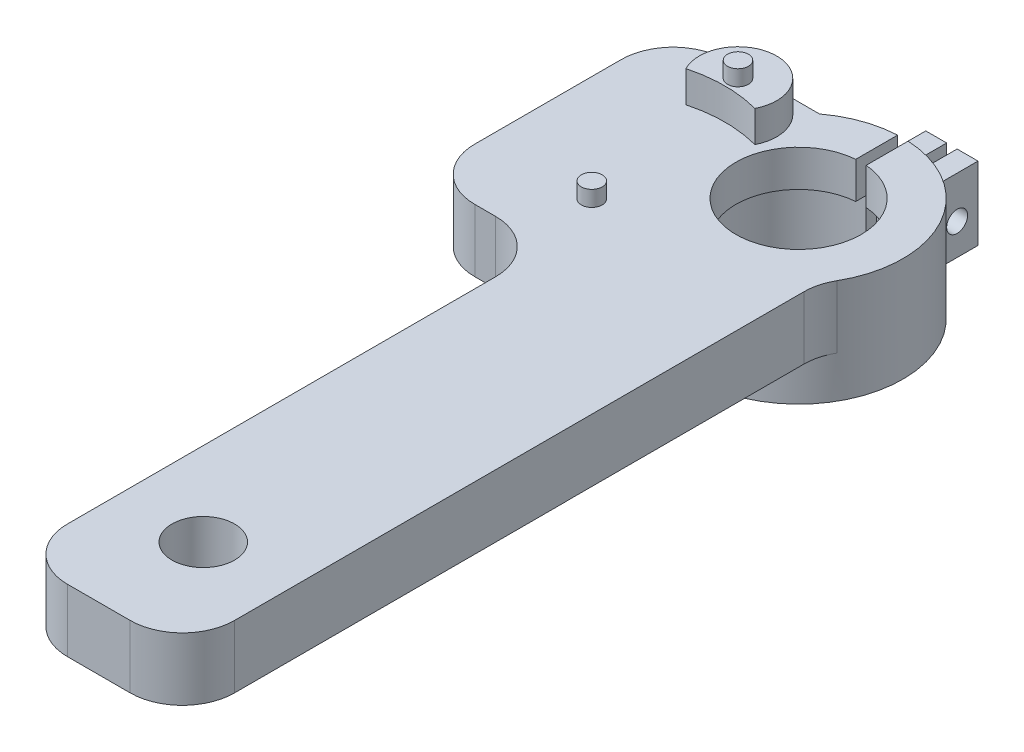
SolidWorks part; units mm, degrees
material "ABS"
ref_plane "Front Plane" through (0, 0, 0) normal (0, 0, 1) x (1, 0, 0)
ref_plane "Top Plane" through (0, 0, 0) normal (0, 1, 0) x (1, 0, 0)
ref_plane "Right Plane" through (0, 0, 0) normal (1, 0, 0) x (0, 0, -1)
sketch "BaseArm" plane through (0, 0, 0) normal (0, 1, 0) x (1, 0, 0)
  line L1 (-8, 0) -> (8, 0)
  line L2 (-8, 0) -> (-8, 62)
  line L3 (-8, 62) -> (8, 62) construction
  line L4 (8, 0) -> (8, 62)
  arc A0 (-8, 62) -> (8, 62) centre (0, 69.6738) ccw
  dimension "D1" = 8
  dimension "D2" = 8
  dimension "D3" = 62
extrude "Boss-Extrude1" add sketch "BaseArm" along normal blind 6
sketch "Sketch2" plane through (0, 0, 0) normal (0, 1, 0) x (1, 0, 0)
  circle A2 centre (0, 67) radius 10
  circle A3 centre (0, 67) radius 7
  dimension "D1" = 14
  dimension "D2" = 20
  dimension "D3" = 67
extrude "Boss-Extrude2" add sketch "Sketch2" along normal blind 6
ref_axis "Axis1" through (0, 7.6937, -67) along (0, -1, 0)
ref_plane "Plane1" through (0, 0, -67) normal (0, 0, 1) x (0, -1, 0)
ref_plane "Plane2" through (0, 0, -77) normal (0, 0, -1) x (-1, 0, 0)
sketch "Sketch14" plane through (0, 0, -77) normal (0, 0, -1) x (-1, 0, 0)
  line L1 (-3, 0) -> (3, 0)
  line L2 (-3, 0) -> (-3, 10)
  line L3 (-3, 10) -> (3, 10)
  line L4 (3, 0) -> (3, 10)
  line L5 (-10, 0) -> (10, 0) construction
  line L6 (0, 7.6937) -> (0, 2.7565) construction
  dimension "D1" = 10
  dimension "D2" = 0
  dimension "D3" = 3
  dimension "D4" = 3
sketch "Sketch24" plane through (0, 0, 0) normal (0, -1, 0) x (1, 0, 0)
  circle A0 centre (0, -67) radius 7
  circle A1 centre (0, -67) radius 10
  arc A2 (-8, -61) -> (8, -61) centre (0, -67) ccw construction
  circle A3 centre (0, -67) radius 7 construction
extrude "Boss-Extrude8" add sketch "Sketch24" along normal blind 4
sketch "Sketch26" plane through (0, 6, 0) normal (0, 1, 0) x (1, 0, 0)
  circle A0 centre (0, 67) radius 7
  circle A1 centre (0, 67) radius 7 construction
  circle A2 centre (0, 67) radius 6
  dimension "D1" = 1
extrude "Boss-Extrude9" add sketch "Sketch26" against normal blind 3.5
sketch "Sketch6" plane through (0, 0, 0) normal (0, 1, 0) x (1, 0, 0)
  line L6 (0, -7.975) -> (0, 7.975) construction
  line L11 (0.5, 83.4083) -> (-0.5, 83.4083)
  line L13 (0.5, 72.3952) -> (-0.5, 72.3952)
  line L14 (-0.5, 83.4083) -> (-0.5, 72.3952)
  line L15 (0.5, 83.4083) -> (0.5, 72.3952)
  dimension "D1" = 1
extrude "Cut-Extrude2" cut sketch "Sketch6" along normal through all and the other way through all
hole_wizard "Ø6.0mm Dowel Hole1" positions "3DSketch3" profile "Sketch9" hole size "Ø6.0" standard "ISO" end condition through all
sketch3d "3DSketch3"
  line L2 (-8, 6, 0) -> (8, 6, 0) construction
  line L3 (0, 6, 0) -> (0, 6, -10) construction
  point P0 (0, 6, -10)
  dimension "D2" = 10
sketch "Sketch9" plane through (0, 6, -10) normal (1, 0, 0) x (0, 0, 1)
  line L0 (0, 0) -> (0, 10)
  line L1 (0, 10) -> (3, 10)
  line L2 (3, 10) -> (3, 0)
  line L5 (3, 0) -> (0, 0)
  line L11 (0, -6.35) -> (0, 107.95) construction
  dimension "Thru Hole Dia." = 6
  dimension "Thru Hole Depth" = 10
sketch "Sketch10" plane through (0, 0, 0) normal (0, 1, 0) x (1, 0, 0)
  line L0 (0, -7.975) -> (0, 7.975) construction
  line L1 (0.5, 0) -> (-0.5, 0)
  line L3 (0.5, 8.5942) -> (-0.5, 8.5942)
  line L4 (-0.5, 0) -> (-0.5, 8.5942)
  line L5 (0.5, 0) -> (0.5, 8.5942)
sketch "Sketch11" plane through (0, 0, 0) normal (0, 1, 0) x (1, 0, 0)
  line L0 (-8, 61) -> (-8, 0) construction
  line L1 (-8, 15.2461) -> (-6, 15.2461)
  line L2 (-8, 15.2461) -> (-8, 57.0454)
  line L3 (-8, 57.0454) -> (-6, 57.0454)
  line L4 (-6, 15.2461) -> (-6, 57.0454)
  line L5 (0, -55) -> (0, 55) construction
  line L6 (8, 57.0454) -> (6, 57.0454)
  line L7 (6, 15.2461) -> (6, 57.0454)
  line L8 (8, 15.2461) -> (6, 15.2461)
  line L9 (8, 15.2461) -> (8, 57.0454)
  dimension "D1" = 2
extrude "Cut-Extrude4" [suppressed] cut sketch "Sketch11" along normal blind 8
ref_point "Point1"
sketch "Sketch27" plane through (0, 6, 0) normal (0, 1, 0) x (1, 0, 0)
  line L0 (-4, 54.5362) -> (-4, 59.5362)
  line L2 (-4, 54.5362) -> (-14, 54.5362)
  line L3 (-14, 54.5362) -> (-14, 75.5362)
  line L4 (-14, 75.5362) -> (-4, 75.5362)
  line L5 (-4, 75.5362) -> (-4, 74.4638)
  arc A0 (-4, 74.4638) -> (-4, 59.5362) centre (0, 67) ccw
  point P1 (-4, 54.5362)
  point P5 (0, 0)
  point P6 (0, 0)
  point P7 (0, 0)
  dimension "D5" = 8.4681
  dimension "D1" = 5
  dimension "D2" = 10
  dimension "D3" = 21
  dimension "D4" = 4
extrude "Boss-Extrude12" [suppressed] add sketch "Sketch27" against normal up to vertex
sketch "Sketch17" plane through (0, 6, 0) normal (0, 1, 0) x (1, 0, 0)
  line L0 (0, 67) -> (-9.851, 57.0522) construction
  line L1 (-9.851, 57.0522) -> (-9.851, 71.0522) construction
  circle A0 centre (-9.851, 57.0522) radius 1
  circle A2 centre (-9.851, 71.0522) radius 1
  dimension "D1" = 2
  dimension "D3" = 14
  dimension "D6" = 2
  dimension "D2" = 14
extrude "Boss-Extrude13" add sketch "Sketch17" along normal blind 1.5
fillet "Fillet2" [suppressed] radius 2
sketch "Sketch28" plane through (0, 7.5, 0) normal (0, 1, 0) x (1, 0, 0)
  circle A0 centre (-9.851, 71.0522) radius 1
extrude "Boss-Extrude14" add sketch "Sketch28" along normal blind 3
sketch "Sketch30" plane through (0, 6, 0) normal (0, 1, 0) x (1, 0, 0)
  circle A0 centre (-9.851, 71.0522) radius 3.7104
extrude "Boss-Extrude15" add sketch "Sketch30" along normal blind 3
sketch "Sketch31" plane through (0, 6, 0) normal (0, 1, 0) x (1, 0, 0)
  circle A0 centre (-9.851, 57.0522) radius 12.75
  circle A1 centre (-9.851, 57.0522) radius 1
  dimension "D1" = 25.5
extrude "Cut-Extrude5" cut sketch "Sketch31" along normal through all
sketch "Sketch32" plane through (0, 6, 0) normal (0, 1, 0) x (1, 0, 0)
  line L0 (-0.5, 76.9875) -> (-0.5, 72.9791) construction
  line L1 (-2.5, 76.6825) -> (-0.5, 76.6825)
  line L2 (-2.5, 76.6825) -> (-2.5, 81.6825)
  line L3 (-2.5, 81.6825) -> (-0.5, 81.6825)
  line L4 (-0.5, 76.6825) -> (-0.5, 81.6825)
  line L5 (0, 67) -> (0, 84.8054) construction
  line L6 (0.5, 76.6825) -> (0.5, 81.6825)
  line L7 (2.5, 81.6825) -> (0.5, 81.6825)
  line L8 (2.5, 76.6825) -> (2.5, 81.6825)
  line L9 (2.5, 76.6825) -> (0.5, 76.6825)
  arc A0 (-0.5, 76.9875) -> (-7.3438, 73.7874) centre (0, 67) ccw construction
  dimension "2.5" = 2
  dimension "D2" = 5
extrude "Boss-Extrude16" add sketch "Sketch32" against normal up to surface (10 mm away) from offset 3 up to face at (0, -4, -66.9924) offset against normal yes
sketch "Sketch34" plane through (2.5, 0, 0) normal (1, 0, 0) x (0, 0, -1)
  line L0 (81.6825, -4) -> (81.6825, 3) construction
  line L1 (76.6825, -4) -> (81.6825, -4) construction
  circle A0 centre (79.6825, -1) radius 1
  dimension "D2" = 2
  dimension "D1" = 2
  dimension "D3" = 3
extrude "Cut-Extrude6" cut sketch "Sketch34" against normal blind 10
sketch "Sketch35" plane through (0, 6, 0) normal (0, 1, 0) x (1, 0, 0)
  line L1 (-20, 51) -> (-6, 51)
  line L2 (-20, 51) -> (-20, 75)
  line L3 (-20, 75) -> (-6, 75)
  line L4 (-6, 51) -> (-6, 59)
  line L5 (-20, 51) -> (-6, 75) construction
  line L6 (-20, 75) -> (-6, 51) construction
  line L7 (-8, 61) -> (-8, 0) construction
  arc A0 (-0.5, 76.9875) -> (-7.3438, 73.7874) centre (0, 67) ccw construction
  arc A2 (-6, 75) -> (-6, 59) centre (0, 67) ccw
  point P0 (-13, 63)
  point P9 (-5.3695, 75.4361)
  dimension "D1" = 24
  dimension "D2" = 14
  dimension "D3" = 2
extrude "Boss-Extrude17" add sketch "Sketch35" against normal up to surface (6 mm away) up to face at (0, 0, -7)
fillet "Fillet3" radius 5 6 edges at (-8, 3, 0) (8, 3, 0) (-20, 3, -51) (-20, 3, -75) (-8, 3, -51) (8, 3, -61)
sketch "Sketch36" plane through (0, 0, 0) normal (0, -1, 0) x (1, 0, 0)
  line L6 (3, 0) -> (-3, 0)
  line L7 (-8, -5) -> (-8, -46)
  line L8 (-13, -51) -> (-15, -51)
  line L9 (-20, -56) -> (-20, -70)
  line L10 (-15, -75) -> (-6, -75)
  line L11 (8, -59.5167) -> (8, -5)
  line L12 (3, 0) -> (-3, 0)
  line L13 (-8, -5) -> (-8, -36.8328)
  line L17 (8, -36.8328) -> (8, -5)
  arc A0 (-8, -36.8328) -> (8, -36.8328) centre (0, -10) ccw
  circle A1 centre (0, -10) radius 3 construction
  circle A2 centre (0, -10) radius 3
  arc A8 (-3, 0) -> (-8, -5) centre (-3, -5) ccw
  arc A9 (-13, -51) -> (-8, -46) centre (-13, -46) ccw
  arc A10 (-15, -51) -> (-20, -56) centre (-15, -56) ccw
  arc A11 (-20, -70) -> (-15, -75) centre (-15, -70) ccw
  arc A12 (8.6667, -62.0111) -> (-6, -75) centre (0, -67) ccw
  arc A13 (8, -59.5167) -> (8.6667, -62.0111) centre (13, -59.5167) ccw
  arc A14 (8, -5) -> (3, 0) centre (3, -5) ccw
  arc A15 (-3, 0) -> (-8, -5) centre (-3, -5) ccw
  arc A21 (8, -5) -> (3, 0) centre (3, -5) ccw
  dimension "D1" = 56
  dimension "D2" = 0
extrude "Boss-Extrude18" add sketch "Sketch36" along normal blind 0.01
